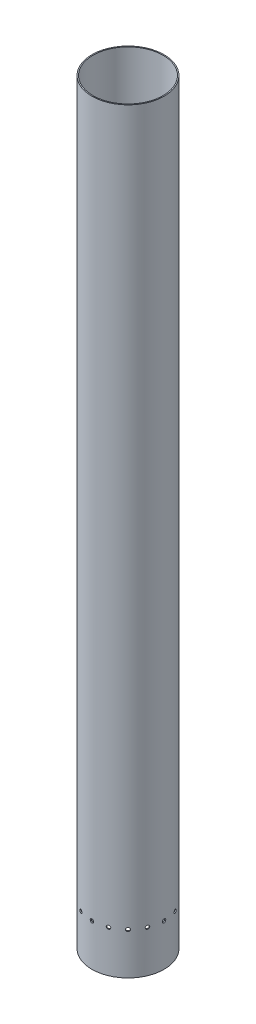
SolidWorks part; units mm, degrees
ref_plane "Front Plane" through (0, 0, 0) normal (0, 0, 1) x (1, 0, 0)
ref_plane "Top Plane" through (0, 0, 0) normal (0, 1, 0) x (1, 0, 0)
ref_plane "Right Plane" through (0, 0, 0) normal (1, 0, 0) x (0, 0, -1)
sketch "Sketch1" plane through (0, 0, 0) normal (0, 1, 0) x (1, 0, 0)
  circle A0 centre (0, 0) radius 63.5
  circle A1 centre (0, 0) radius 65.405
  dimension "D1" = 127
  dimension "D2" = 130.81
extrude "Boss-Extrude1" add sketch "Sketch1" against normal blind 1371.6
ref_plane "Plane1" through (0, 0, 65.405) normal (0, 0, 1) x (1, 0, 0)
ref_axis "Axis1" through (0, -1371.6, 0) along (0, 1, 0)
sketch "Sketch2" plane through (0, 0, 65.405) normal (0, 0, 1) x (1, 0, 0)
  line L0 (-65.405, -1371.6) -> (65.405, -1371.6) construction
  circle A0 centre (0, -1295.4) radius 3.175
  point P2 (0, 0)
  point P3 (0, 0)
  dimension "D1" = 6.35
  dimension "D2" = 76.2
extrude "Cut-Extrude1" cut sketch "Sketch2" against normal up to next contours A0
pattern_circular "CirPattern1" count 16 over 360 about axis through (0, -1371.6, 0) along (0, 1, 0) of "Cut-Extrude1"
